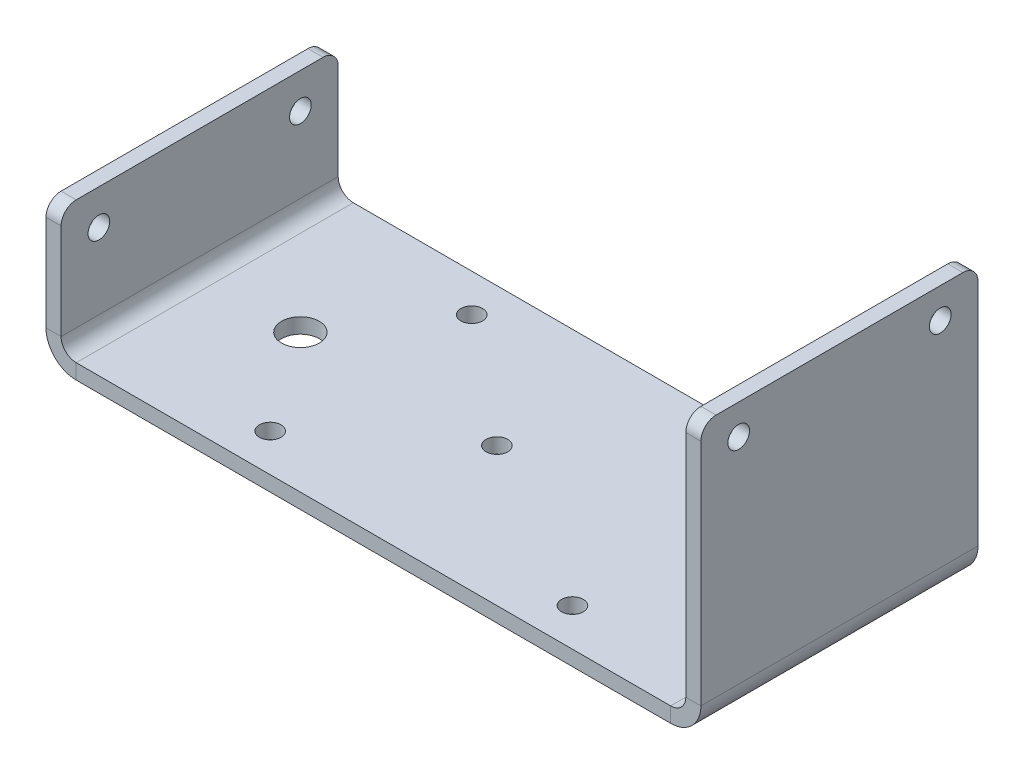
SolidWorks part; units mm, degrees
note: The reader was unsure of these and kept them because the rebuilt part matched: flange length of "Edge-Flange1", "Edge-Flange2".
material "3.3549 (EN-AW 5182)"
ref_plane "Front Plane" through (0, 0, 0) normal (0, 0, 1) x (1, 0, 0)
ref_plane "Top Plane" through (0, 0, 0) normal (0, 1, 0) x (1, 0, 0)
ref_plane "Right Plane" through (0, 0, 0) normal (1, 0, 0) x (0, 0, -1)
sketch "Sketch1" plane through (0, 0, 0) normal (0, 1, 0) x (1, 0, 0)
  line L0 (-44.2539, 0) -> (44.2539, 0) construction
  line L1 (-59, -27.5) -> (65, -27.5)
  line L2 (-59, -27.5) -> (-59, 27.5)
  line L3 (-59, 27.5) -> (65, 27.5)
  line L4 (65, -27.5) -> (65, 27.5)
  line L5 (0, -44.7868) -> (0, 44.7868) construction
  circle A0 centre (-25, 20) radius 1
  circle A1 centre (35, 20) radius 1
  circle A2 centre (-25, -20) radius 1
  circle A3 centre (35, -20) radius 1
  circle A4 centre (45, 0) radius 3.75
  circle A5 centre (-39, 0) radius 3.75
  circle A6 centre (0, 0) radius 1
  point P0 (1.1809, 0)
  point P5 (-59, 0)
  point P9 (3, 27.5)
  dimension "D3" = 20
  dimension "D7" = 2
  dimension "D8" = 7.5
  dimension "D11" = 20
  dimension "D12" = 2
  dimension "D1" = 55
  dimension "D2" = 124
  dimension "D4" = 20
  dimension "D5" = 25
  dimension "D6" = 35
  dimension "D9" = 65
  dimension "D10" = 20
base flange "Base-Flange1" sketch "Sketch1" thickness 3 reverse thickness direction no parameters "D1"=3
edge flange "Edge-Flange1" sketch "Sketch8" flange angle 90 flange length 28 flange position material outside bend radius 3 thickness 3 relief rectangular parameters "D1"=2.5, "D6"=10
sketch "Sketch8" plane through (-59, 0, 0) normal (-1, 0, 0) x (0, 0, 1)
  line L0 (-27.5, 0) -> (27.5, 0) construction
  line L1 (-27.5, 0) -> (27.5, 0)
  line L2 (-27.5, 0) -> (-27.5, 25)
  line L3 (-27.5, 25) -> (27.5, 25)
  line L4 (27.5, 25) -> (27.5, 0)
  circle A0 centre (20, 18) radius 1
  circle A1 centre (-20, 18) radius 1
  dimension "D1" = 7.5
  dimension "D4" = 2
  dimension "D5" = 25
  dimension "D2" = 7.5
  dimension "D3" = 7
bend "EdgeBend1" bend radius 3 bend angle 90 parameters "D5"=1
ref_plane "Plane1" through (65, 0, 27.5) normal (0, 0, -1) x (-1, 0, 0)
edge flange "Edge-Flange2" sketch "Sketch14" flange angle 90 flange length 54.5 flange position material outside bend radius 3 thickness 3 relief rectangular parameters "D1"=2.5, "D6"=10
sketch "Sketch14" plane through (65, 0, 0) normal (1, 0, 0) x (0, 0, -1)
  line L0 (-27.5, 0) -> (27.5, 0) construction
  line L1 (-27.5, 0) -> (27.5, 0)
  line L2 (-27.5, 0) -> (-27.5, 51.5)
  line L4 (27.5, 51.5) -> (27.5, 0)
  line L14 (-27.5, 51.5) -> (27.5, 51.5)
  circle A0 centre (-20, 45.5) radius 1
  circle A1 centre (20, 45.5) radius 1
  dimension "D1" = 2
  dimension "D2" = 6
  dimension "D3" = 7.5
  dimension "D4" = 51.5
  dimension "D5" = 7.5
bend "EdgeBend2" bend radius 3 bend angle 90 parameters "D5"=2
sketch "Sketch17" plane through (68, 0, 0) normal (1, 0, 0) x (0, 0, -1)
  point P0 (-20, 45.5)
  point P3 (20, 45.5)
hole_wizard "M4 Clearance Hole1" positions "Sketch17" profile "Sketch16" hole size "M4" standard "ANSI Metric" end condition up to next
sketch "Sketch16" plane through (68, 45.5, 20) normal (0, 1, 0) x (0, 0, -1)
  line L0 (0, 0) -> (0, 130)
  line L1 (0, 130) -> (2.15, 130)
  line L2 (2.15, 130) -> (2.15, 0)
  line L5 (2.15, 0) -> (0, 0)
  line L11 (0, -6.35) -> (0, 107.95) construction
  dimension "Thru Hole Dia." = 4.3
  dimension "Thru Hole Depth" = 130
sketch "Sketch20" plane through (-62, 0, 0) normal (-1, 0, 0) x (0, 0, 1)
  point P0 (-20, 18)
  point P3 (20, 18)
hole_wizard "M4 Clearance Hole2" positions "Sketch20" profile "Sketch19" hole size "M4" standard "ANSI Metric"
sketch "Sketch19" plane through (-62, 18, -20) normal (0, 1, 0) x (0, 0, 1)
  line L0 (0, 0) -> (0, 4.2919)
  line L1 (0, 4.2919) -> (2.15, 3)
  line L2 (2.15, 3) -> (2.15, 0)
  line L5 (2.15, 0) -> (0, 0)
  line L10 (0, 4.2919) -> (-2.15, 3) construction
  line L11 (0, -6.35) -> (0, 107.95) construction
  dimension "Hole Dia." = 4.3
  dimension "Hole Depth" = 3
  dimension "Drill Angle" = 118
sketch "Sketch23" plane through (0, -3, 0) normal (0, -1, 0) x (-1, 0, 0)
  point P0 (-35, 20)
  point P3 (25, 20)
  point P6 (25, -20)
  point P9 (-35, -20)
  point P12 (0, 0)
hole_wizard "M4 Clearance Hole3" positions "Sketch23" profile "Sketch22" hole size "M4" standard "ANSI Metric"
sketch "Sketch22" plane through (35, -3, -20) normal (1, 0, 0) x (0, 0, -1)
  line L0 (0, 0) -> (0, 4.2919)
  line L1 (0, 4.2919) -> (2.15, 3)
  line L2 (2.15, 3) -> (2.15, 0)
  line L5 (2.15, 0) -> (0, 0)
  line L10 (0, 4.2919) -> (-2.15, 3) construction
  line L11 (0, -6.35) -> (0, 107.95) construction
  dimension "Hole Dia." = 4.3
  dimension "Hole Depth" = 3
  dimension "Drill Angle" = 118
fillet "Fillet1" radius 3 4 edges at (-60.5, 25, 27.5) (-60.5, 25, -27.5) (66.5, 51.5, 27.5) (66.5, 51.5, -27.5)
sketch "Bend-Lines1" [suppressed] plane through (0, 0, 0) normal (0, 1, 0) x (1, 0, 0)
sketch "Bounding-Box1" [suppressed] plane through (0, 0, 0) normal (0, 1, 0) x (1, 0, 0)
sheet metal parameters "Sheet-Metal8" thickness 3 parameters "D1"=3
flat pattern "Flat-Pattern8" [suppressed]
sketch "Bend-Lines2" plane through (0, 0, 0) normal (0, 1, 0) x (1, 0, 0)
sketch3d "Bounding-Box2" [suppressed]
  line L0 (-55, 25, 0) -> (55, 25, 0) construction
  line L1 (-55, -25, 0) -> (55, -25, 0) construction
  line L2 (-55, 25, 0) -> (-55, -25, 0) construction
  line L3 (55, 25, 0) -> (55, -25, 0) construction
sheet metal parameters "Sheet-Metal9" thickness 3 parameters "D1"=3
flat pattern "Flat-Pattern8"
sketch "Bend-Lines2" plane through (0, 0, 0) normal (0, 1, 0) x (1, 0, 0)
  line L0 (-55.3197, 25) -> (-55.3197, -25) construction
  line L1 (-55.3197, 25) -> (-55.3197, -25) construction
sketch3d "Bounding-Box2" [suppressed]
  line L0 (55, 25, 0) -> (-72.6394, 25, 0) construction
  line L1 (55, -25, 0) -> (-72.6394, -25, 0) construction
  line L2 (55, 25, 0) -> (55, -25, 0) construction
  line L3 (-72.6394, 25, 0) -> (-72.6394, -25, 0) construction
bend of the flat pattern "Flatten-<EdgeBend1>1"
sheet metal parameters "Sheet-Metal10" thickness 3 parameters "D1"=3
flat pattern "Flat-Pattern8"
sketch "Bend-Lines2" plane through (0, 0, 0) normal (0, 1, 0) x (1, 0, 0)
  line L0 (-63.8197, 25) -> (-63.8197, -25) construction
  line L1 (-63.8197, 25) -> (-63.8197, -25) construction
  line L2 (53.8197, -25) -> (53.8197, 25) construction
  line L3 (53.8197, -25) -> (53.8197, 25) construction
sketch3d "Bounding-Box2" [suppressed]
  line L0 (99.1394, 25, 0) -> (-86.1394, 25, 0) construction
  line L1 (99.1394, -25, 0) -> (-86.1394, -25, 0) construction
  line L2 (99.1394, 25, 0) -> (99.1394, -25, 0) construction
  line L3 (-86.1394, 25, 0) -> (-86.1394, -25, 0) construction
bend of the flat pattern "Flatten-<EdgeBend1>1"
bend of the flat pattern "Flatten-<EdgeBend2>1"
sheet metal parameters "Sheet-Metal11" thickness 3 parameters "D1"=3
flat pattern "Flat-Pattern8"
sketch "Bend-Lines2" plane through (0, 0, 0) normal (0, 1, 0) x (1, 0, 0)
  line L0 (-63.8197, 25) -> (-63.8197, -25) construction
  line L1 (-63.8197, 25) -> (-63.8197, -25) construction
  line L2 (53.8197, -25) -> (53.8197, 25) construction
  line L3 (53.8197, -25) -> (53.8197, 25) construction
sketch3d "Bounding-Box2" [suppressed]
  line L0 (99.1394, 25, 0) -> (-86.1394, 25, 0) construction
  line L1 (99.1394, -25, 0) -> (-86.1394, -25, 0) construction
  line L2 (99.1394, 25, 0) -> (99.1394, -25, 0) construction
  line L3 (-86.1394, 25, 0) -> (-86.1394, -25, 0) construction
bend of the flat pattern "Flatten-<EdgeBend1>1"
bend of the flat pattern "Flatten-<EdgeBend2>1"
sheet metal parameters "Sheet-Metal12" thickness 3 parameters "D1"=3
flat pattern "Flat-Pattern8"
sketch "Bend-Lines2" plane through (0, 0, 0) normal (0, 1, 0) x (1, 0, 0)
  line L0 (-63.8197, 25) -> (-63.8197, -25) construction
  line L1 (-63.8197, 25) -> (-63.8197, -25) construction
  line L2 (53.8197, -25) -> (53.8197, 25) construction
  line L3 (53.8197, -25) -> (53.8197, 25) construction
sketch3d "Bounding-Box2" [suppressed]
  line L0 (99.1394, 25, 0) -> (-86.1394, 25, 0) construction
  line L1 (99.1394, -25, 0) -> (-86.1394, -25, 0) construction
  line L2 (99.1394, 25, 0) -> (99.1394, -25, 0) construction
  line L3 (-86.1394, 25, 0) -> (-86.1394, -25, 0) construction
bend of the flat pattern "Flatten-<EdgeBend1>1"
bend of the flat pattern "Flatten-<EdgeBend2>1"
sheet metal parameters "Sheet-Metal13" thickness 3 parameters "D1"=3
flat pattern "Flat-Pattern8"
sketch "Bend-Lines2" plane through (0, 0, 0) normal (0, 1, 0) x (1, 0, 0)
  line L0 (-59.1, 27.5) -> (-59.1, -27.5) construction
  line L1 (-59.1, 27.5) -> (-59.1, -27.5) construction
  line L2 (65.1, -27.5) -> (65.1, 27.5) construction
  line L3 (65.1, -27.5) -> (65.1, 27.5) construction
sketch3d "Bounding-Box2" [suppressed]
  line L0 (116.7, 27.5, 0) -> (-84.2, 27.5, 0) construction
  line L1 (116.7, -27.5, 0) -> (-84.2, -27.5, 0) construction
  line L2 (116.7, 27.5, 0) -> (116.7, -27.5, 0) construction
  line L3 (-84.2, 27.5, 0) -> (-84.2, -27.5, 0) construction
bend of the flat pattern "Flatten-<EdgeBend1>1"
bend of the flat pattern "Flatten-<EdgeBend2>1"
